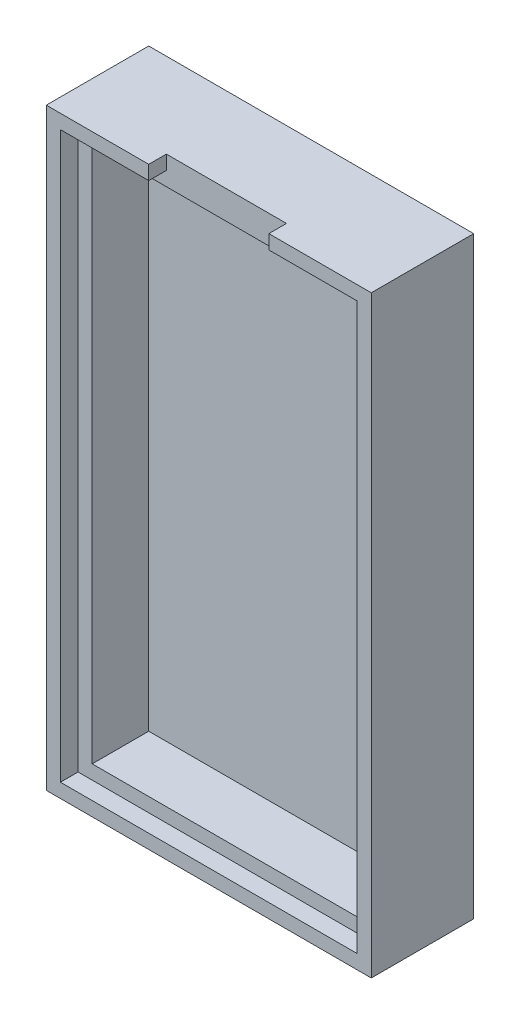
SolidWorks part; units mm, degrees
ref_plane "Front Plane" through (0, 0, 0) normal (0, 0, 1) x (1, 0, 0)
ref_plane "Top Plane" through (0, 0, 0) normal (0, 1, 0) x (1, 0, 0)
ref_plane "Right Plane" through (0, 0, 0) normal (1, 0, 0) x (0, 0, -1)
sketch "Sketch1" plane through (0, 0, 0) normal (0, 0, 1) x (1, 0, 0)
  line L1 (-14.605, 26.67) -> (14.605, 26.67)
  line L2 (-14.605, 26.67) -> (-14.605, -26.67)
  line L3 (-14.605, -26.67) -> (14.605, -26.67)
  line L4 (14.605, 26.67) -> (14.605, -26.67)
  point P4 (0, 26.67)
  point P6 (-14.605, 0)
  dimension "D1" = 53.34
  dimension "D2" = 29.21
extrude "Boss-Extrude1" add sketch "Sketch1" along normal mid plane 9.2075
shell "Shell1" thickness 2.54 removed face at (0, 0, 4.6037)
sketch "Sketch2" plane through (0, 26.67, 0) normal (0, 1, 0) x (1, 0, 0)
  line L0 (14.605, -4.6037) -> (-14.605, -4.6037) construction
  line L1 (-5.3975, -4.6037) -> (5.3975, -4.6037)
  line L2 (-5.3975, -4.6037) -> (-5.3975, -3.0162)
  line L3 (-5.3975, -3.0162) -> (5.3975, -3.0162)
  line L4 (5.3975, -4.6037) -> (5.3975, -3.0162)
  point P6 (0, -3.0162)
  dimension "D1" = 10.795
  dimension "D2" = 1.5875
extrude "Cut-Extrude1" cut sketch "Sketch2" against normal up to surface (2.54 mm away) up to face at (0, 24.13, 1.27)
sketch "Sketch3" plane through (0, 0, 4.6037) normal (0, 0, 1) x (1, 0, 0)
  line L17 (13.335, -25.4) -> (13.335, 25.4)
  line L18 (-13.335, -25.4) -> (13.335, -25.4)
  line L19 (-13.335, 25.4) -> (-13.335, -25.4)
  line L20 (13.335, 25.4) -> (-13.335, 25.4)
  line L21 (13.335, -25.4) -> (13.335, 25.4)
  line L22 (-13.335, -25.4) -> (13.335, -25.4)
  line L23 (-13.335, 25.4) -> (-13.335, -25.4)
  line L24 (13.335, 25.4) -> (-13.335, 25.4)
  dimension "D1" = 1.27
extrude "Cut-Extrude2" cut sketch "Sketch3" against normal up to surface (1.5875 mm away) up to face at (0, 25.4, 3.0162)
